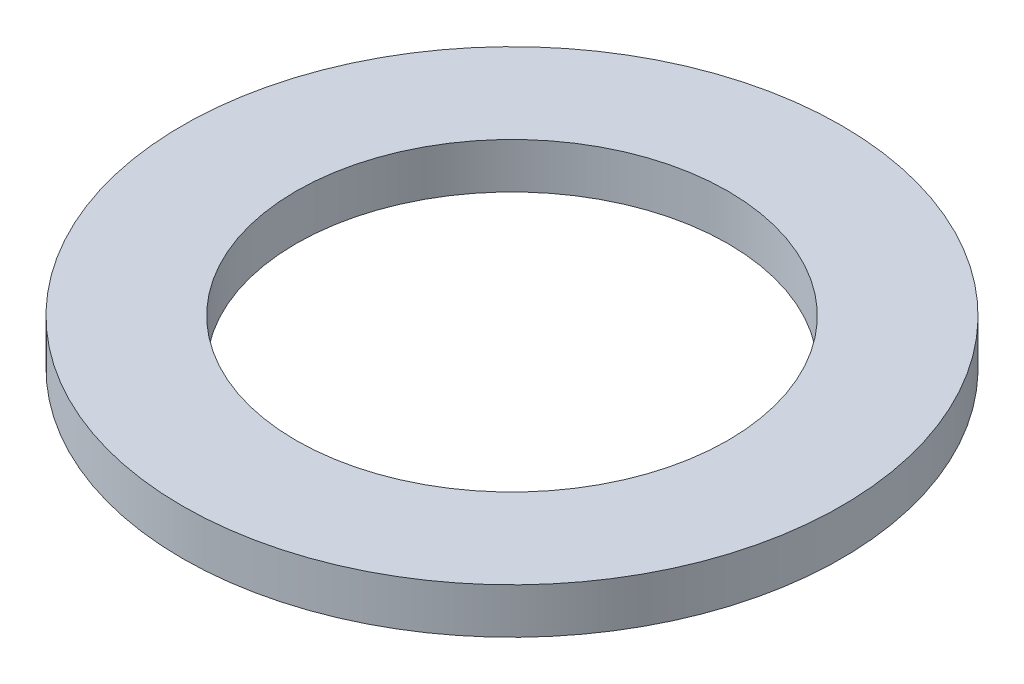
SolidWorks part; units mm, degrees
ref_plane "Front Plane" through (0, 0, 0) normal (0, 0, 1) x (1, 0, 0)
ref_plane "Top Plane" through (0, 0, 0) normal (0, 1, 0) x (1, 0, 0)
ref_plane "Right Plane" through (0, 0, 0) normal (1, 0, 0) x (0, 0, -1)
sketch "Sketch1" plane through (0, 0, 0) normal (0, 1, 0) x (1, 0, 0)
  circle A0 centre (0, 0) radius 72.5
  dimension "FLANGE_OD" = 145
extrude "Boss-Extrude1" add sketch "Sketch1" along normal blind 10
sketch "Sketch2" plane through (0, 0, 0) normal (0, 1, 0) x (1, 0, 0)
  circle A0 centre (0, 0) radius 47.5
  dimension "BORE_D" = 95
extrude "Cut-Extrude1" cut sketch "Sketch2" along normal through all
sketch "Sketch3" plane through (0, 10, 0) normal (0, 1, 0) x (1, 0, 0)
  circle A0 centre (0, 0) radius 26.3392 construction
  circle A1 centre (-26.3392, 0) radius 2.162
  dimension "BOLT_D" = 4.324
  dimension "BOLT_PCD" = 52.6784
extrude "Cut-Extrude2" cut sketch "Sketch3" against normal blind 6.4195 rebuild error yes
pattern_circular "CirPattern1" count 5 over 360 rebuild error yes
